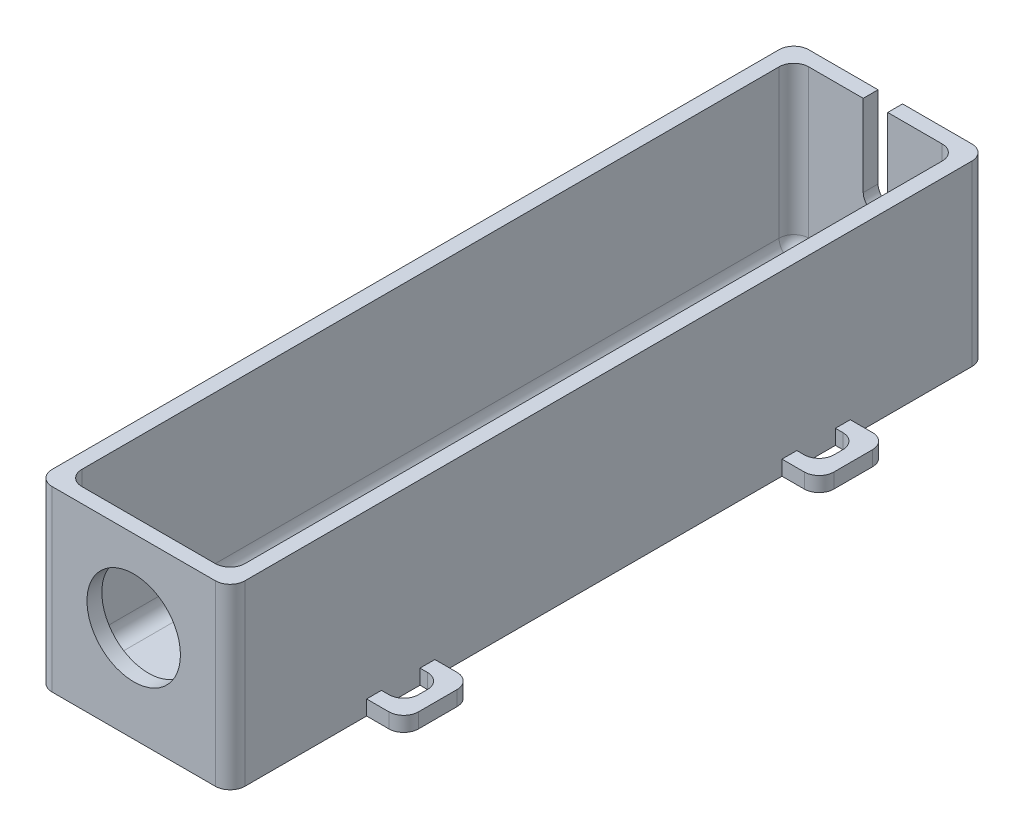
SolidWorks part; units mm, degrees
ref_plane "Front Plane" through (0, 0, 0) normal (0, 0, 1) x (1, 0, 0)
ref_plane "Top Plane" through (0, 0, 0) normal (0, 1, 0) x (1, 0, 0)
ref_plane "Right Plane" through (0, 0, 0) normal (1, 0, 0) x (0, 0, -1)
sketch "Sketch4" plane through (0, 0, 0) normal (0, 0, 1) x (1, 0, 0)
  line L0 (-16.25, -16.25) -> (-16.25, 13.75)
  line L1 (-13.75, -13.75) -> (13.75, -13.75)
  line L2 (-13.75, -13.75) -> (-13.75, 13.75)
  line L4 (13.75, -13.75) -> (13.75, 13.75)
  line L5 (-13.75, -13.75) -> (13.75, 13.75) construction
  line L6 (-13.75, 13.75) -> (13.75, -13.75) construction
  line L8 (16.25, -16.25) -> (16.25, 13.75)
  line L9 (-16.25, -16.25) -> (16.25, -16.25)
  line L10 (-13.75, 13.75) -> (-16.25, 13.75)
  line L11 (-16.25, 13.75) -> (-13.75, 13.75)
  line L12 (-16.25, -16.25) -> (-16.25, 16.25) construction
  line L13 (-13.75, 13.75) -> (13.75, 13.75) construction
  line L14 (13.75, 13.75) -> (16.25, 13.75)
  line L15 (-16.25, 16.25) -> (16.25, 16.25) construction
  line L16 (16.25, -16.25) -> (16.25, 16.25) construction
  point P0 (0, 0)
  dimension "D1" = 27.5
  dimension "D2" = 27.5
  dimension "D3" = 2.5
extrude "Boss-Extrude2" add sketch "Sketch4" along normal blind 61.25 and the other way blind 61.25 contours L14 L4 L1 L2 L10 L0 L9 L8 region at (-15.8077, -1.25, 0)
sketch "Sketch5" plane through (0, 0, 61.25) normal (0, 0, 1) x (1, 0, 0)
  line L0 (-13.75, 13.75) -> (13.75, 13.75)
  line L8 (16.25, 13.75) -> (13.75, 13.75)
  line L9 (13.75, 13.75) -> (13.75, -13.75)
  line L10 (13.75, -13.75) -> (-13.75, -13.75)
  line L11 (-13.75, -13.75) -> (-13.75, 13.75)
  line L12 (-13.75, 13.75) -> (-16.25, 13.75)
  line L13 (-16.25, 13.75) -> (-16.25, -16.25)
  line L14 (-16.25, -16.25) -> (16.25, -16.25)
  line L15 (16.25, -16.25) -> (16.25, 13.75)
  line L16 (16.25, 13.75) -> (13.75, 13.75)
  line L17 (13.75, 13.75) -> (13.75, -13.75)
  line L18 (13.75, -13.75) -> (-13.75, -13.75)
  line L19 (-13.75, -13.75) -> (-13.75, 13.75)
  line L20 (-13.75, 13.75) -> (-16.25, 13.75)
  line L21 (-16.25, 13.75) -> (-16.25, -16.25)
  line L22 (-16.25, -16.25) -> (16.25, -16.25)
  line L23 (16.25, -16.25) -> (16.25, 13.75)
  circle A0 centre (0, 0) radius 7.875
  line M9 (16.25, 13.75) -> (13.75, 13.75)
  line M10 (13.75, 13.75) -> (13.75, -13.75)
  line M11 (13.75, -13.75) -> (-13.75, -13.75)
  line M12 (-13.75, -13.75) -> (-13.75, 13.75)
  line M13 (-13.75, 13.75) -> (-16.25, 13.75)
  line M14 (-16.25, 13.75) -> (-16.25, -16.25)
  line M15 (-16.25, -16.25) -> (16.25, -16.25)
  line M16 (16.25, -16.25) -> (16.25, 13.75)
  dimension "D1" = 0
extrude "Boss-Extrude3" add sketch "Sketch5" along normal blind 2.5 contours M16 M9 M10 M11 M12 M13 M14 M15 | L0 A0 M12 M11 M10 region at (0, 13.3611, 61.25) region at (-14.1923, 0, 61.25)
sketch "Sketch7" plane through (0, 0, -61.25) normal (0, 0, -1) x (-1, 0, 0)
  line L0 (-13.75, 13.75) -> (13.75, 13.75)
  line L1 (-13.75, 13.75) -> (13.75, 13.75)
  line L2 (-2.0625, 0) -> (-2.0625, 13.75)
  line L3 (2.0625, 0) -> (2.0625, 13.75)
  line L8 (-13.75, 13.75) -> (-16.25, 13.75)
  line L9 (-16.25, 13.75) -> (-16.25, -16.25)
  line L10 (-16.25, -16.25) -> (16.25, -16.25)
  line L11 (16.25, -16.25) -> (16.25, 13.75)
  line L12 (16.25, 13.75) -> (13.75, 13.75)
  line L13 (13.75, 13.75) -> (13.75, -13.75)
  line L14 (13.75, -13.75) -> (-13.75, -13.75)
  line L15 (-13.75, -13.75) -> (-13.75, 13.75)
  line L16 (-13.75, 13.75) -> (-16.25, 13.75)
  line L17 (-16.25, 13.75) -> (-16.25, -16.25)
  line L18 (-16.25, -16.25) -> (16.25, -16.25)
  line L19 (16.25, -16.25) -> (16.25, 13.75)
  line L20 (16.25, 13.75) -> (13.75, 13.75)
  line L21 (13.75, 13.75) -> (13.75, -13.75)
  line L22 (13.75, -13.75) -> (-13.75, -13.75)
  line L23 (-13.75, -13.75) -> (-13.75, 13.75)
  circle A0 centre (0, 0) radius 2.0625
  line M10 (-13.75, 13.75) -> (-16.25, 13.75)
  line M11 (-16.25, 13.75) -> (-16.25, -16.25)
  line M12 (-16.25, -16.25) -> (16.25, -16.25)
  line M13 (16.25, -16.25) -> (16.25, 13.75)
  line M14 (16.25, 13.75) -> (13.75, 13.75)
  line M15 (13.75, 13.75) -> (13.75, -13.75)
  line M16 (13.75, -13.75) -> (-13.75, -13.75)
  line M17 (-13.75, -13.75) -> (-13.75, 13.75)
  dimension "D1" = 0
extrude "Boss-Extrude4" add sketch "Sketch7" along normal blind 2.5 contours M17 M10 M11 M12 M13 M14 M15 M16 | A0 L2 L0 L3 M17 M16 M15 region at (14.1923, 0, -61.25) region at (7.9062, 13.3611, -61.25)
sketch "Sketch8" plane through (0, -16.25, 0) normal (0, -1, 0) x (1, 0, 0)
  line L0 (0, 0) -> (0, 7.0404)
  line L1 (0, -16.5) -> (0, 16.5) construction
  line L2 (0, 7.0404) -> (0, 0)
  line L3 (5.982, 0) -> (0, 0)
  line L4 (16.5, 0) -> (-16.5, 0) construction
  line L5 (16.25, 0) -> (16.25, 35)
  line L6 (16.25, -63.75) -> (16.25, 63.75) construction
  line L8 (16.25, 31.75) -> (20, 31.75)
  line L11 (20, 31.75) -> (20, 38.25)
  line L12 (16.25, 35) -> (20, 38.25) construction
  line L13 (16.25, 35) -> (20, 31.75) construction
  line L15 (22.5, 29.25) -> (22.5, 40.75)
  line L16 (16.25, 29.25) -> (22.5, 29.25)
  line L17 (10, 40.75) -> (22.5, 40.75) construction
  line L18 (12.5, 38.25) -> (20, 38.25) construction
  line L19 (12.5, 31.75) -> (20, 31.75) construction
  line L20 (10, 29.25) -> (22.5, 29.25) construction
  line L21 (12.5, 31.75) -> (12.5, 38.25) construction
  line L22 (10, 29.25) -> (10, 40.75) construction
  line L23 (16.25, 31.75) -> (16.25, 29.25)
  line L24 (16.25, 29.25) -> (16.25, 40.75)
  line L25 (16.25, 40.75) -> (22.5, 40.75)
  line L26 (20, 38.25) -> (16.25, 38.25)
  line L27 (16.25, 38.25) -> (16.25, 35)
  line L28 (-16.25, 29.25) -> (-22.5, 29.25)
  line L29 (-22.5, 29.25) -> (-22.5, 40.75)
  line L30 (-16.25, 40.75) -> (-22.5, 40.75)
  line L31 (-16.25, 29.25) -> (-16.25, 40.75)
  line L32 (-20, 31.75) -> (-20, 38.25)
  line L33 (-16.25, 31.75) -> (-20, 31.75)
  line L34 (-20, 38.25) -> (-16.25, 38.25)
  line L35 (20, -38.25) -> (16.25, -38.25)
  line L36 (20, -31.75) -> (20, -38.25)
  line L37 (16.25, -31.75) -> (20, -31.75)
  line L38 (16.25, -29.25) -> (22.5, -29.25)
  line L39 (22.5, -29.25) -> (22.5, -40.75)
  line L40 (16.25, -40.75) -> (22.5, -40.75)
  line L41 (16.25, -29.25) -> (16.25, -40.75)
  line L42 (-16.25, -31.75) -> (-20, -31.75)
  line L43 (-20, -38.25) -> (-16.25, -38.25)
  line L44 (-20, -31.75) -> (-20, -38.25)
  line L45 (-16.25, -29.25) -> (-16.25, -40.75)
  line L46 (-16.25, -40.75) -> (-22.5, -40.75)
  line L47 (-22.5, -29.25) -> (-22.5, -40.75)
  line L48 (-16.25, -29.25) -> (-22.5, -29.25)
  line L49 (-16.25, 40.75) -> (-16.25, -40.75)
  line L50 (16.25, -40.75) -> (16.25, -29.25)
  line M6 (16.25, -63.75) -> (16.25, 63.75)
  line M8 (-16.25, 63.75) -> (-16.25, -63.75)
  dimension "D1" = 35
  dimension "D3" = 6.5
  dimension "D4" = 2.5
extrude "Boss-Extrude5" add sketch "Sketch8" against normal blind 2.5 contours L26 L11 L8 L5 L16 L15 L25 L24 | L32 L34 L30 L29 L28 L31 L33 M8 | L40 L39 L38 L37 L36 L35 M6 | L48 L47 L46 L43 L44 L42 M8 region at (20.0164, -16.25, 35) region at (20.0164, -16.25, -35) region at (-20.0164, -16.25, 35) region at (-20.0164, -16.25, -35)
fillet "Fillet1" radius 2.5 28 edges at (0, -13.75, -61.25) (13.75, -13.75, 0) (0, -13.75, 61.25) (-13.75, -13.75, 0) (-20, -15, -31.75) (-22.5, -15, -29.25) (-22.5, -15, -40.75) (-20, -15, -38.25) (-20, -15, 31.75) (-20, -15, 38.25) (-22.5, -15, 29.25) (-22.5, -15, 40.75) (20, -15, -38.25) (20, -15, -31.75) (22.5, -15, -40.75) (22.5, -15, -29.25) (20, -15, 38.25) (20, -15, 31.75) (22.5, -15, 40.75) (22.5, -15, 29.25) (-16.25, -1.25, -63.75) (16.25, -1.25, -63.75) (16.25, -1.25, 63.75) (-16.25, -1.25, 63.75) (13.75, 0, 61.25) (-13.75, 0, 61.25) (-13.75, 0, -61.25) (13.75, 0, -61.25)
sketch "Sketch9" plane through (0, -16.25, 0) normal (0, -1, 0) x (1, 0, 0)
  line L0 (7.1622, 31.2921) -> (4.7255, 33.9554)
  line L2 (13.75, -63.75) -> (-13.75, -63.75) construction
  line L3 (-10.0301, -63.75) -> (4.6293, -63.75)
  line L4 (-6.3134, 42.9948) -> (-4.4332, 39.8624)
  line L5 (9.8136, 27.2216) -> (9.8136, 23.0715)
  line L6 (-0.9748, 18.6989) -> (-10.0301, 14.1196)
  line L7 (-10.0301, 14.1196) -> (-10.0301, 18.0788)
  line L8 (-10.0301, 18.0788) -> (-1.3803, 22.4514)
  line L9 (-1.3803, 22.4514) -> (-1.3803, 23.6599)
  line L10 (-1.3803, 23.6599) -> (-10.0301, 23.6599)
  line L11 (-10.0301, 23.6599) -> (-10.0301, 27.2216)
  line L12 (-10.0301, 27.2216) -> (9.8136, 27.2216)
  line L13 (2.1814, 23.6599) -> (2.1814, 22.2725)
  line L14 (6.2519, 22.4474) -> (6.2519, 23.6599)
  line L15 (6.2519, 23.6599) -> (2.1814, 23.6599)
  line L16 (9.8136, 5.0842) -> (9.8136, 1.7808)
  line L17 (9.8136, 1.7808) -> (-10.0301, -6.233)
  line L18 (-10.0301, -6.233) -> (-10.0301, -2.4288)
  line L19 (-10.0301, -2.4288) -> (-5.9596, -0.8864)
  line L20 (-5.9596, -0.8864) -> (-5.9596, 7.7594)
  line L21 (-5.9596, 7.7594) -> (-10.0301, 9.3018)
  line L22 (-10.0301, 9.3018) -> (-10.0301, 13.102)
  line L23 (-10.0301, 13.102) -> (9.8136, 5.0842)
  line L24 (4.4909, 3.4345) -> (-2.3979, 6.4079)
  line L25 (-2.3979, 6.4079) -> (-2.3979, 0.4611)
  line L26 (-2.3979, 0.4611) -> (4.4909, 3.4345)
  line L27 (9.8136, -9.1587) -> (9.8136, -12.7204)
  line L28 (9.8136, -12.7204) -> (-3.0975, -12.7204)
  line L29 (-2.6245, -18.5717) -> (9.8136, -18.5717)
  line L30 (9.8136, -18.5717) -> (9.8136, -22.1334)
  line L31 (9.8136, -22.1334) -> (-2.0243, -22.1334)
  line L32 (-2.0243, -9.1587) -> (9.8136, -9.1587)
  line L33 (9.8136, -25.0591) -> (9.8136, -28.8633)
  line L34 (9.8136, -28.8633) -> (-4.2821, -33.9633)
  line L35 (-4.2821, -33.9633) -> (9.8136, -39.0753)
  line L36 (9.8136, -39.0753) -> (9.8136, -42.8676)
  line L37 (9.8136, -42.8676) -> (-10.0301, -35.6726)
  line L38 (-10.0301, -35.6726) -> (-10.0301, -32.2421)
  line L39 (-10.0301, -32.2421) -> (9.8136, -25.0591)
  spline S0 degree 3 poles (4.7255, 33.9554) (5.0386, 34.1682) (5.4691, 34.504) (5.9636, 34.997) (6.2501, 35.3552) (6.4803, 35.7125) (6.6895, 36.1874) (6.7618, 36.5628) (6.7607, 36.8095) knots 0 0 0 0 0.311848 0.448466 0.574275 0.689054 0.797558 1 1 1 1
  spline S1 degree 3 poles (6.7607, 36.8095) (6.7611, 37.0263) (6.7224, 37.3494) (6.5416, 37.7282) (6.37, 37.9693) (6.1632, 38.1601) (5.8792, 38.3606) (5.6242, 38.4136) (5.4609, 38.4155) knots 0 0 0 0 0.285993 0.416634 0.54738 0.671583 0.784401 1 1 1 1
  spline S2 degree 3 poles (5.4609, 38.4155) (5.2943, 38.4179) (4.9544, 38.3546) (4.6515, 38.1892) (4.5108, 38.0855) knots 0 0 0 0 0.487115 1 1 1 1
  spline S3 degree 3 poles (4.5108, 38.0855) (4.3753, 37.9839) (4.1624, 37.7866) (3.8547, 37.4828) (3.5546, 37.1746) (3.2144, 36.8098) (2.6735, 36.2098) (2.2479, 35.7304) (1.9508, 35.3904) knots 0 0 0 0 0.136348 0.233803 0.34864 0.483185 0.635971 1 1 1 1
  spline S4 degree 3 poles (1.9508, 35.3904) (1.6757, 35.0745) (1.2892, 34.6214) (0.793, 34.0599) (0.4872, 33.7126) (0.2225, 33.4195) (-0.0471, 33.1311) (-0.2287, 32.9417) (-0.3388, 32.8344) knots 0 0 0 0 0.366184 0.520457 0.655012 0.770624 0.865677 1 1 1 1
  spline S5 degree 3 poles (-0.3388, 32.8344) (-0.6967, 32.4909) (-1.2433, 32.0279) (-2.008, 31.5205) (-2.5566, 31.2409) (-3.1114, 31.0366) (-3.8811, 30.8335) (-4.4842, 30.7833) (-4.8903, 30.7833) knots 0 0 0 0 0.289911 0.417498 0.535597 0.648803 0.762441 1 1 1 1
  spline S6 degree 3 poles (-4.8903, 30.7833) (-5.2839, 30.7769) (-5.8636, 30.8347) (-6.61, 31.0012) (-7.1303, 31.1886) (-7.6264, 31.4195) (-8.0985, 31.7007) (-8.5356, 32.0445) (-8.9494, 32.4264) (-9.321, 32.8554) (-9.648, 33.317) (-9.9262, 33.8103) (-10.1466, 34.3371) (-10.3234, 34.8943) (-10.4953, 35.6942) (-10.5405, 36.319) (-10.539, 36.7419) knots 0 0 0 0 0.12791 0.189023 0.248512 0.307568 0.366978 0.426948 0.4883 0.550066 0.611349 0.67219 0.734048 0.796945 0.862267 1 1 1 1
  spline S7 degree 3 poles (-10.539, 36.7419) (-10.5387, 37.078) (-10.5093, 37.5756) (-10.4027, 38.2216) (-10.29, 38.6823) (-10.1483, 39.1267) (-9.9721, 39.5544) (-9.7646, 39.965) (-9.5258, 40.361) (-9.2487, 40.7397) (-8.9391, 41.1063) (-8.5902, 41.4561) (-8.2088, 41.7963) (-7.7852, 42.1149) (-7.1672, 42.5421) (-6.6609, 42.8161) (-6.3134, 42.9948) knots 0 0 0 0 0.125885 0.186265 0.245009 0.303398 0.360818 0.418085 0.47554 0.533815 0.593678 0.655095 0.718735 0.784946 0.853503 1 1 1 1
  spline S8 degree 3 poles (-4.4332, 39.8624) (-4.8228, 39.6491) (-5.3624, 39.3022) (-5.9808, 38.7643) (-6.3422, 38.3614) (-6.6256, 37.9452) (-6.8949, 37.3761) (-6.9779, 36.9152) (-6.9773, 36.6108) knots 0 0 0 0 0.307612 0.442139 0.566229 0.681222 0.789558 1 1 1 1
  spline S9 degree 3 poles (-6.9773, 36.6108) (-6.9804, 36.311) (-6.9097, 35.8701) (-6.6723, 35.3336) (-6.4202, 34.9943) (-6.1323, 34.7067) (-5.705, 34.4326) (-5.34, 34.3396) (-5.097, 34.345) knots 0 0 0 0 0.275349 0.405274 0.536299 0.66224 0.777967 1 1 1 1
  spline S10 degree 3 poles (-5.097, 34.345) (-4.8665, 34.3457) (-4.5149, 34.4145) (-4.0711, 34.6162) (-3.7889, 34.7923) (-3.5536, 34.9762) (-3.3528, 35.1565) (-3.1263, 35.3701) (-2.8803, 35.6225) (-2.6101, 35.9089) (-2.1989, 36.3583) (-1.8884, 36.7219) (-1.6745, 36.9765) knots 0 0 0 0 0.155074 0.238325 0.327891 0.378865 0.43968 0.509886 0.588921 0.677472 0.775572 1 1 1 1
  spline S11 degree 3 poles (-1.6745, 36.9765) (-1.2663, 37.4629) (-0.6688, 38.1554) (0.1217, 39.0159) (0.6535, 39.5606) (1.1473, 40.0344) (1.5985, 40.4432) (2.0161, 40.7779) (2.5116, 41.13) (3.1123, 41.4691) (4.0614, 41.8487) (4.8019, 41.9827) (5.2899, 41.9772) knots 0 0 0 0 0.215221 0.309931 0.395996 0.473179 0.541879 0.602267 0.654475 0.747781 0.835263 1 1 1 1
  spline S12 degree 3 poles (5.2899, 41.9772) (5.6248, 41.979) (6.1214, 41.9292) (6.7614, 41.7752) (7.2185, 41.6124) (7.6528, 41.3938) (8.0712, 41.1353) (8.4728, 40.8316) (8.8446, 40.4791) (9.19, 40.0967) (9.4932, 39.6871) (9.7482, 39.2546) (9.9628, 38.8023) (10.1242, 38.3243) (10.2811, 37.6491) (10.3202, 37.1236) (10.3224, 36.7698) knots 0 0 0 0 0.124481 0.184877 0.244614 0.304595 0.365488 0.427421 0.49161 0.55586 0.618978 0.68088 0.742424 0.804953 0.868227 1 1 1 1
  spline S13 degree 3 poles (10.3224, 36.7698) (10.3218, 36.304) (10.2354, 35.6048) (9.9524, 34.7083) (9.704, 34.1642) (9.4552, 33.735) (9.2311, 33.405) (8.9729, 33.0686) (8.6794, 32.7239) (8.3526, 32.373) (7.8497, 31.886) (7.4493, 31.5256) (7.1622, 31.2921) knots 0 0 0 0 0.212967 0.319763 0.429089 0.485862 0.546561 0.611431 0.679818 0.753594 0.83076 1 1 1 1
  spline S14 degree 3 poles (9.8136, 23.0715) (9.8165, 22.5439) (9.7976, 21.7828) (9.7401, 20.81) (9.6769, 20.1708) (9.595, 19.5937) (9.4957, 19.0776) (9.3835, 18.6221) (9.246, 18.2212) (9.0877, 17.8603) (8.9089, 17.5249) (8.703, 17.209) (8.4783, 16.9068) (8.2268, 16.6237) (7.9505, 16.3605) (7.6514, 16.1138) (7.3312, 15.8833) (6.9905, 15.6782) (6.634, 15.4965) (6.2609, 15.3472) (5.8732, 15.2229) (5.4705, 15.1273) (4.905, 15.0384) (4.4709, 15.0043) (4.1769, 15.01) knots 0 0 0 0 0.140162 0.202243 0.258851 0.310778 0.357037 0.398448 0.435299 0.469507 0.503055 0.536158 0.569602 0.603019 0.636633 0.67089 0.705962 0.741342 0.776451 0.812145 0.847995 0.884542 0.921987 1 1 1 1
  spline S15 degree 3 poles (4.1769, 15.01) (3.8704, 15.0147) (3.4178, 15.0339) (2.8321, 15.1299) (2.4218, 15.2366) (2.0272, 15.3593) (1.6555, 15.5225) (1.3013, 15.7066) (0.9696, 15.9253) (0.6531, 16.1653) (0.364, 16.4444) (0.0865, 16.7446) (-0.1618, 17.0827) (-0.3977, 17.4438) (-0.6892, 17.9759) (-0.8704, 18.4025) (-0.9748, 18.6989) knots 0 0 0 0 0.134789 0.198536 0.260386 0.320962 0.379904 0.438503 0.496154 0.554265 0.612749 0.672513 0.733646 0.79679 0.861936 1 1 1 1
  spline S16 degree 3 poles (2.1814, 22.2725) (2.1861, 21.948) (2.1877, 21.4801) (2.2448, 20.8869) (2.2965, 20.5037) (2.3561, 20.1597) (2.4416, 19.8578) (2.5331, 19.5934) (2.6472, 19.37) (2.7748, 19.1785) (2.9262, 19.0179) (3.0919, 18.8764) (3.2826, 18.7654) (3.4903, 18.6759) (3.8055, 18.5985) (4.053, 18.5665) (4.2246, 18.5717) knots 0 0 0 0 0.202122 0.290736 0.370617 0.442748 0.507764 0.565672 0.616562 0.663447 0.708377 0.753458 0.798569 0.845127 0.893728 1 1 1 1
  spline S17 degree 3 poles (4.2246, 18.5717) (4.4309, 18.5693) (4.7378, 18.6179) (5.109, 18.7879) (5.3609, 18.9596) (5.5819, 19.1759) (5.7751, 19.4237) (5.9315, 19.7066) (6.0316, 19.9705) (6.0932, 20.2122) (6.1369, 20.4296) (6.1707, 20.6821) (6.2035, 20.9681) (6.2261, 21.2891) (6.2484, 21.786) (6.2491, 22.1758) (6.2519, 22.4474) knots 0 0 0 0 0.125251 0.185397 0.246785 0.309395 0.3725 0.436991 0.505001 0.543261 0.588403 0.639621 0.697924 0.763292 0.834993 1 1 1 1
  spline S18 degree 3 poles (-3.0975, -12.7204) (-3.3562, -12.716) (-3.7272, -12.7326) (-4.2018, -12.7568) (-4.5125, -12.7877) (-4.7929, -12.8334) (-5.0449, -12.8776) (-5.2639, -12.9375) (-5.5133, -13.0274) (-5.7935, -13.166) (-6.0855, -13.3925) (-6.352, -13.6538) (-6.5739, -13.967) (-6.7532, -14.319) (-6.9359, -14.8517) (-6.9715, -15.2856) (-6.9773, -15.5785) knots 0 0 0 0 0.13949 0.20037 0.256433 0.307804 0.353659 0.39442 0.430156 0.496666 0.562018 0.628755 0.69741 0.768079 0.841338 1 1 1 1
  spline S19 degree 3 poles (-6.9773, -15.5785) (-6.9801, -15.8918) (-6.9252, -16.3518) (-6.7315, -16.9244) (-6.5262, -17.3007) (-6.2836, -17.6348) (-6.0003, -17.9121) (-5.6908, -18.1404) (-5.3995, -18.2839) (-5.1338, -18.3671) (-4.8945, -18.4216) (-4.6144, -18.4685) (-4.2949, -18.5084) (-3.9338, -18.5331) (-3.3738, -18.57) (-2.9318, -18.5691) (-2.6245, -18.5717) knots 0 0 0 0 0.153651 0.225206 0.29531 0.36319 0.427095 0.488999 0.551225 0.585358 0.625416 0.671592 0.724656 0.783348 0.849131 1 1 1 1
  spline S20 degree 3 poles (-2.0243, -22.1334) (-2.4854, -22.134) (-3.1484, -22.128) (-3.9936, -22.0884) (-4.541, -22.0533) (-5.0317, -22.0111) (-5.4656, -21.9566) (-5.8423, -21.8899) (-6.2712, -21.79) (-6.765, -21.6177) (-7.3336, -21.3399) (-7.8902, -20.9872) (-8.4289, -20.5704) (-8.9293, -20.0998) (-9.3687, -19.5859) (-9.739, -19.0373) (-10.036, -18.4496) (-10.2652, -17.8186) (-10.4769, -16.8885) (-10.5441, -16.1579) (-10.539, -15.658) knots 0 0 0 0 0.112566 0.161777 0.206504 0.246443 0.281985 0.313198 0.339791 0.389396 0.440456 0.493937 0.549959 0.606468 0.661298 0.71467 0.767607 0.821627 0.878109 1 1 1 1
  spline S21 degree 3 poles (-10.539, -15.658) (-10.5402, -15.3204) (-10.5069, -14.8222) (-10.4063, -14.1733) (-10.2987, -13.7109) (-10.1593, -13.2644) (-9.9892, -12.8345) (-9.7843, -12.4239) (-9.554, -12.0312) (-9.3016, -11.6583) (-9.0264, -11.3141) (-8.7402, -10.9936) (-8.4372, -10.7026) (-8.1185, -10.4392) (-7.7836, -10.2038) (-7.4326, -9.9968) (-7.0591, -9.8128) (-6.6442, -9.6553) (-6.1731, -9.5226) (-5.6383, -9.4066) (-5.0387, -9.3205) (-4.3764, -9.2423) (-3.365, -9.1735) (-2.5729, -9.1636) (-2.0243, -9.1587) knots 0 0 0 0 0.082306 0.121576 0.160073 0.198001 0.235575 0.272725 0.309812 0.346569 0.382461 0.417249 0.451311 0.484834 0.518013 0.551052 0.584156 0.619453 0.659145 0.70346 0.752831 0.806837 0.866137 1 1 1 1
extrude "Cut-Extrude1" cut sketch "Sketch9" against normal blind 0.6 contours S13 S12 S11 S10 S9 S8 L4 S7 S6 S5 S4 S3 S2 S1 S0 L0 | S15 S14 L5 L12 L11 L10 L9 L8 L7 L6 S17 S16 L13 L15 L14 | L23 L22 L21 L20 L19 L18 L17 L16 L26 L25 L24 | S21 S20 L31 L30 L29 S19 S18 L28 L27 L32 | L39 L38 L37 L36 L35 L34 L33 region at (-0.4154, -16.25, 36.5842) region at (0.4051, -16.25, 21.6744) region at (9.5366, -16.25, 3.4325) region at (9.5722, -16.25, -10.9395) region at (9.547, -16.25, -26.9612)
